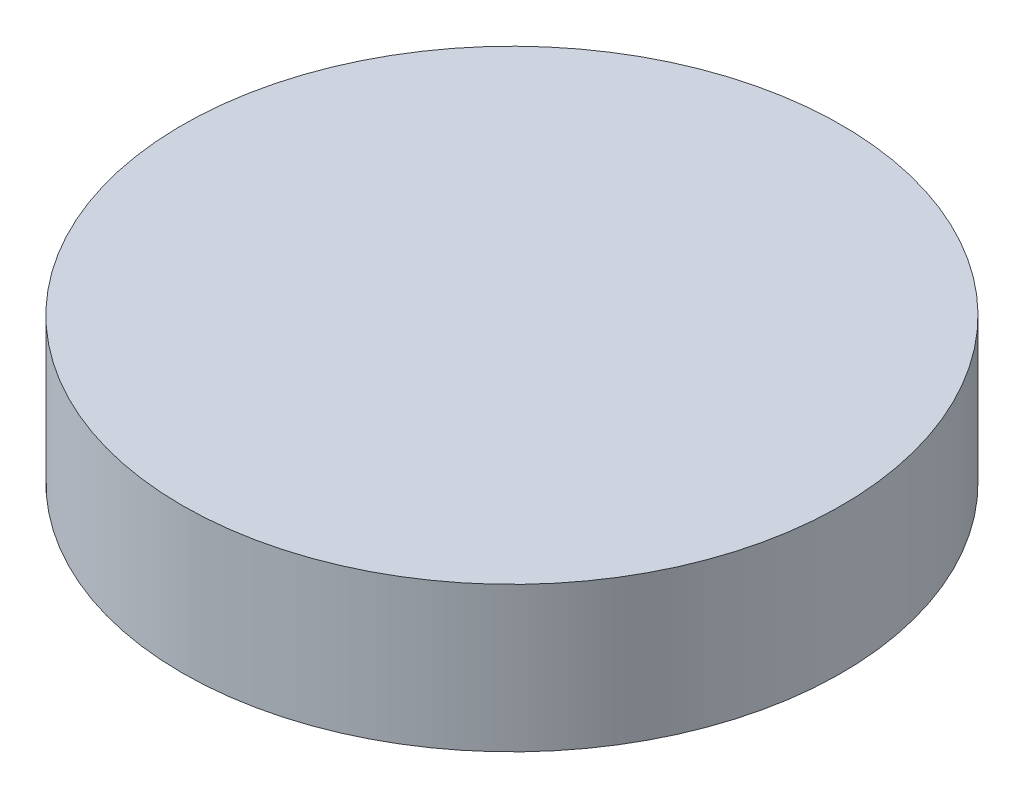
SolidWorks part; units mm, degrees
ref_plane "Ebene vorne" through (0, 0, 0) normal (0, 0, 1) x (1, 0, 0)
ref_plane "Ebene oben" through (0, 0, 0) normal (0, 1, 0) x (1, 0, 0)
ref_plane "Ebene rechts" through (0, 0, 0) normal (1, 0, 0) x (0, 0, -1)
sketch "Sketch1" plane through (0, 0, 0) normal (0, 1, 0) x (1, 0, 0)
  circle A0 centre (0, 0) radius 72.7
  dimension "D1" = 145.4
extrude "Boss-Extrude1" add sketch "Sketch1" along normal blind 32
sketch "Sketch2" plane through (0, 32, 0) normal (0, 1, 0) x (1, 0, 0)
  line L0 (0, 0) -> (0, 66.4755) construction
  circle A0 centre (0, 50) radius 4
  dimension "D1" = 8
  dimension "D2" = 50
